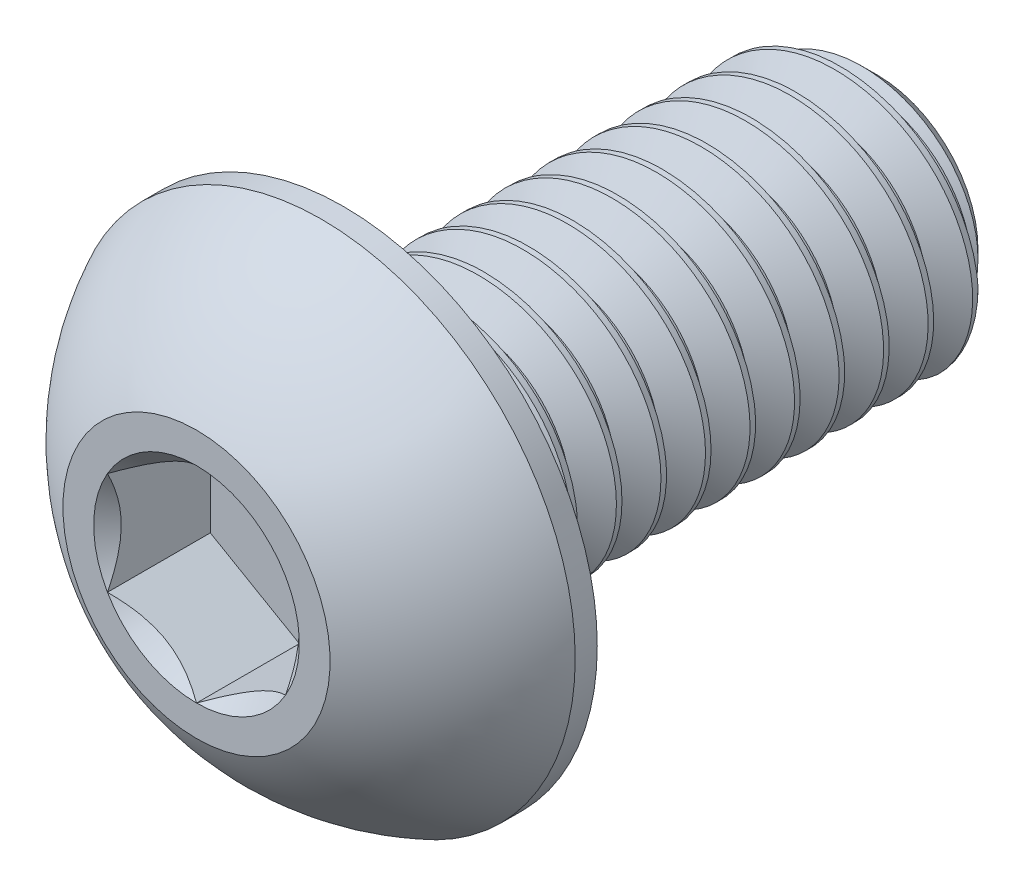
SolidWorks part; units mm, degrees
ref_plane "Front" through (0, 0, 0) normal (0, 0, 1) x (1, 0, 0)
ref_plane "Top" through (0, 0, 0) normal (0, 1, 0) x (1, 0, 0)
ref_plane "Right" through (0, 0, 0) normal (1, 0, 0) x (0, 0, -1)
sketch "Sketch1" plane through (0, 0, 0) normal (1, 0, 0) x (0, 0, -1)
  line L2 (1.65, 1.5) -> (7.65, 1.5)
  line L3 (7.65, 1.5) -> (7.65, 0)
  line L4 (7.65, 0) -> (1.65, 0)
  line L6 (1.4025, 2.85) -> (1.65, 2.85) construction
  line L7 (7.65, 1.5) -> (7.65, -1.5) construction
  line L8 (0, 0) -> (1.65, 0) construction
  line L9 (1.65, 2.85) -> (1.65, -2.85) construction
  line L11 (1.65, 1.5) -> (1.65, 0)
  line L13 (0, 1) -> (0, -1) construction
  line L14 (0, 1) -> (0, 1.5) construction
  arc A3 (0, 1.5) -> (1.4025, 2.85) centre (2.7948, 0) cw construction
  dimension "D1" = 0.2475
  dimension "Head Ht" = 1.65
  dimension "Head Dia" = 5.7
  dimension "Dia" = 3
  dimension "Lg" = 6
  dimension "Hex" = 2
revolve "Revolve1" add sketch "Sketch1" angle 360 about L4
sketch "Sketch3" plane through (0, 0, -7.65) normal (0, 0, -1) x (-1, 0, 0)
  circle A0 centre (0, 0) radius 1.5
curve "Helix/Spiral1" pitch 0.5 height 6.5 radius 1.5 centre (0, 0, -7.65) axis (0, 0, 1) start towards (0, 1, 0)
sketch "Sketch2" plane through (0, 0, 0) normal (1, 0, 0) x (0, 0, -1)
  line L0 (7.65, 1.5) -> (8.0875, 1.5)
  line L1 (8.0875, 1.5) -> (7.9, 1.1752)
  line L2 (7.9, 1.1752) -> (7.8375, 1.1752)
  line L3 (7.8375, 1.1752) -> (7.65, 1.5)
  line L4 (7.7438, 1.3376) -> (7.9938, 1.3376) construction
  dimension "D1" = 60
  dimension "D2" = 0.0625
  dimension "D3" = 0.25
chamfer "Chamfer1" distance 0.375 angle 45 1 edges at (0, 1.5, -7.65)
sweep "Cut-Sweep1" cut profiles "Sketch2" path "Helix/Spiral1"
sketch "Sketch7" plane through (0, 0, 0) normal (1, 0, 0) x (0, 0, -1)
  line L6 (1.4025, 2.85) -> (1.65, 2.85) construction
  line L8 (0, 0) -> (1.65, 0) construction
  line L11 (1.65, 2.85) -> (1.65, -2.85) construction
  line L12 (1.4025, 2.85) -> (1.65, 2.85)
  line L13 (0, 0) -> (1.65, 0)
  line L14 (0, 1) -> (0, -1) construction
  line L15 (1.65, 2.85) -> (1.65, 0)
  line L16 (0, 1.5) -> (0, 0)
  arc A2 (1.4025, 2.85) -> (0, 1.5) centre (2.7948, 0) ccw construction
  arc A3 (1.4025, 2.85) -> (0, 1.5) centre (2.7948, 0) ccw
revolve "Revolve2" add sketch "Sketch7" angle 360 about L13
sketch "Sketch5" plane through (0, 0, 0) normal (0, 0, 1) x (1, 0, 0)
  line L1 (1, -0.5774) -> (1, 0.5774)
  line L2 (1, 0.5774) -> (0, 1.1547)
  line L3 (0, 1.1547) -> (-1, 0.5774)
  line L4 (-1, 0.5774) -> (-1, -0.5774)
  line L5 (-1, -0.5774) -> (0, -1.1547)
  line L6 (0, -1.1547) -> (1, -0.5774)
  circle A0 centre (0, 0) radius 1 construction
extrude "Cut-Extrude2" cut sketch "Sketch5" against normal blind 1.155
sketch "Sketch6" plane through (0, 0, 0) normal (0, 0, 1) x (1, 0, 0)
  circle A0 centre (0, 0) radius 1.1547
extrude "Cut-Extrude3" cut sketch "Sketch6" against normal blind 1.155 draft 45
sketch "Sketch9" [suppressed] plane through (0, 0, -4.2164) normal (0, 0, 1) x (1, 0, 0)
  circle A2 centre (0, 0) radius 3.9687
extrude "Boss-Extrude2" [suppressed] add sketch "Sketch9" against normal offset from surface (9.525 mm away) 28.575 up to face at (0, 1.125, -7.65)
sketch "Sketch10" plane through (0, 0, 0) normal (1, 0, 0) x (0, 0, -1)
  line L0 (7.65, 1.5) -> (7.65, -1.5) construction
  point P0 (6.9, -1.5)
  dimension "D1" = 0.75
equation "\"D3@Helix/Spiral1\" = \"Lg@Sketch1\" + \"D4@Helix/Spiral1\""
equation "\"D2@Sketch2\" = \"D4@Helix/Spiral1\" * .125"
equation "\"D3@Sketch2\" = \"D4@Helix/Spiral1\" * .5"
equation "\"D1@Chamfer1\" = \"D4@Helix/Spiral1\" * .75"
equation "\"D1@Cut-Extrude2\" = \"Head Ht@Sketch1\" * .7"
equation "\"D1@Sketch1\" = \"Head Ht@Sketch1\" * .15"
equation "\"D1@Sketch10\" = \"D4@Helix/Spiral1\" * 1.5"
equation "\"D1@Cut-Extrude3\" = \"D1@Cut-Extrude2\""
